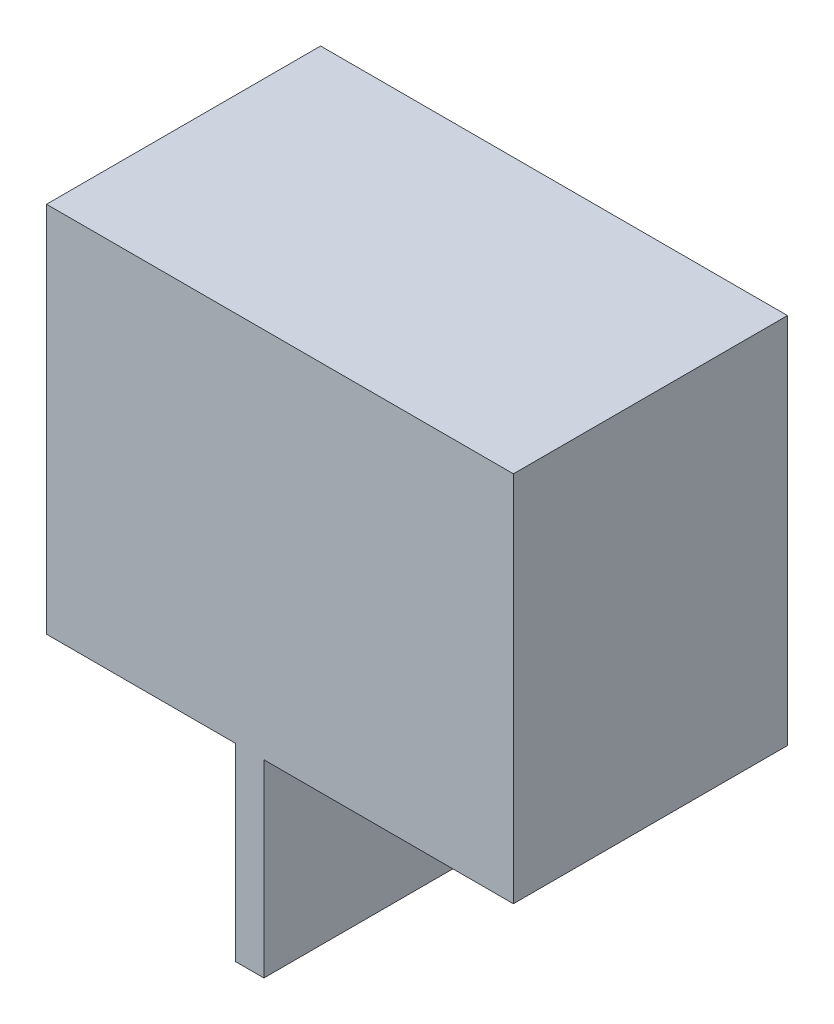
SolidWorks part; units mm, degrees
ref_plane "Front Plane" through (0, 0, 0) normal (0, 0, 1) x (1, 0, 0)
ref_plane "Top Plane" through (0, 0, 0) normal (0, 1, 0) x (1, 0, 0)
ref_plane "Right Plane" through (0, 0, 0) normal (1, 0, 0) x (0, 0, -1)
sketch "Sketch2" plane through (0, 0, 0) normal (0, 0, 1) x (1, 0, 0)
  line L1 (0, 0) -> (42.418, 0)
  line L2 (0, 0) -> (0, 42.418)
  line L3 (0, 42.418) -> (42.418, 42.418)
  line L4 (42.418, 0) -> (42.418, 42.418)
  line L5 (-3.81, 46.228) -> (46.228, 46.228)
  line L6 (-3.81, 46.228) -> (-3.81, -3.81)
  line L7 (-3.81, -3.81) -> (46.228, -3.81)
  line L8 (46.228, 46.228) -> (46.228, -3.81)
  dimension "D1" = 42.418
  dimension "D2" = 42.418
  dimension "D3" = 3.81
  dimension "D4" = 3.81
  dimension "D5" = 3.81
  dimension "D6" = 3.81
extrude "Boss-Extrude1" add sketch "Sketch2" along normal blind 34.29
sketch "Sketch4" plane through (0, 0, 34.29) normal (0, 0, 1) x (1, 0, 0)
  line L1 (-3.81, 46.228) -> (46.228, 46.228)
  line L2 (-3.81, 46.228) -> (-3.81, -3.81)
  line L3 (-3.81, -3.81) -> (46.228, -3.81)
  line L4 (46.228, 46.228) -> (46.228, -3.81)
extrude "Boss-Extrude2" add sketch "Sketch4" along normal blind 2.54
sketch "Sketch5" plane through (0, 0, 0) normal (0, 0, -1) x (-1, 0, 0)
  line L6 (3.81, -3.81) -> (-46.228, -3.81) construction
  line L7 (-12.7, -3.81) -> (-8.89, -3.81)
  line L8 (-12.7, -3.81) -> (-12.7, -29.21)
  line L9 (-12.7, -29.21) -> (-8.89, -29.21)
  line L10 (-8.89, -3.81) -> (-8.89, -29.21)
  line L11 (3.81, 46.228) -> (3.81, -3.81) construction
  dimension "D1" = 12.7
  dimension "D2" = 3.81
  dimension "D3" = 25.4
extrude "Boss-Extrude3" add sketch "Sketch5" against normal up to surface (36.83 mm away) up to face at (21.209, 21.209, 36.83)
sketch "Sketch6" plane through (0, 0, 0) normal (0, 0, -1) x (-1, 0, 0)
  line L0 (-46.228, 46.228) -> (3.81, 46.228) construction
  line L1 (3.81, -3.81) -> (16.51, -3.81)
  line L2 (3.81, -3.81) -> (3.81, 46.228)
  line L3 (3.81, 46.228) -> (16.51, 46.228)
  line L4 (16.51, -3.81) -> (16.51, 46.228)
  dimension "D1" = 0
  dimension "D2" = 12.7
extrude "Boss-Extrude4" add sketch "Sketch6" against normal up to surface (36.83 mm away) up to face at (16.002, 2.3495, 36.83)
